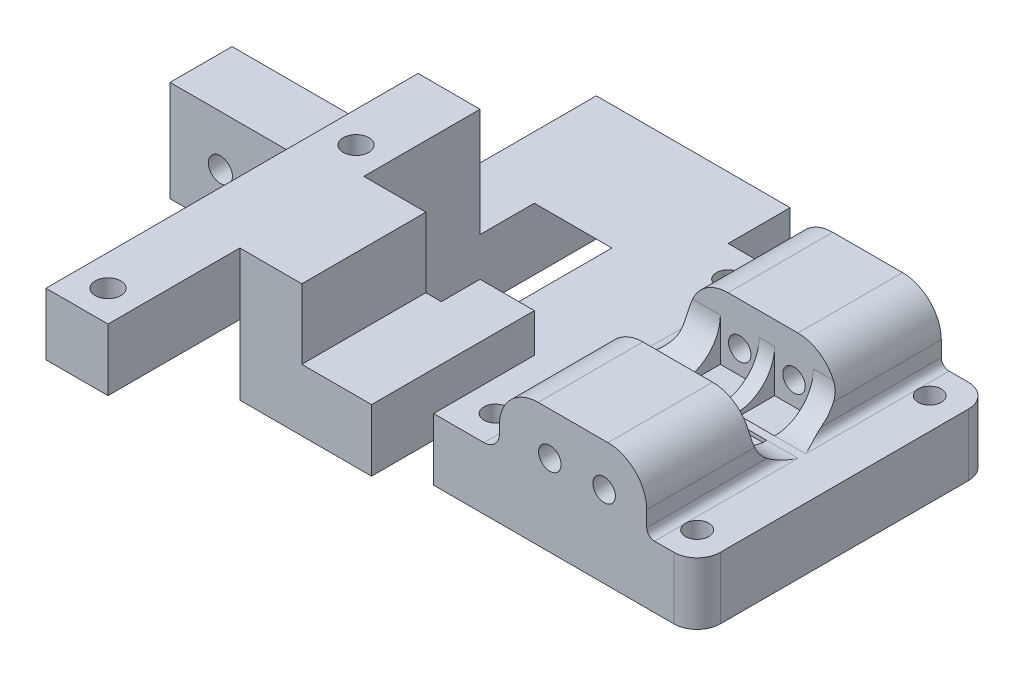
SolidWorks part; units mm, degrees
ref_plane "Front" through (0, 0, 0) normal (0, 0, 1) x (1, 0, 0)
ref_plane "Top" through (0, 0, 0) normal (0, 1, 0) x (1, 0, 0)
ref_plane "Right" through (0, 0, 0) normal (1, 0, 0) x (0, 0, -1)
sketch "Sketch1" plane through (0, 0, 0) normal (0, 1, 0) x (1, 0, 0)
  line L1 (0, 0) -> (300, 0)
  line L2 (0, 0) -> (0, -20)
  line L3 (0, -20) -> (300, -20)
  line L4 (300, 0) -> (300, -20)
  dimension "D1" = 20
  dimension "D2" = 300
extrude "Boss-Extrude1" add sketch "Sketch1" along normal blind 8
sketch "Sketch2" plane through (0, 0, 20) normal (0, 0, 1) x (1, 0, 0)
  line L0 (0, 8) -> (300, 8) construction
  line L1 (0, 0) -> (34, 0)
  line L2 (0, 0) -> (0, 8)
  line L3 (0, 8) -> (34, 8)
  line L4 (34, 0) -> (34, 8)
  line L5 (266, 8) -> (300, 8)
  line L6 (300, 0) -> (300, 8)
  line L7 (266, 0) -> (300, 0)
  line L8 (266, 0) -> (266, 8)
  dimension "D1" = 34
  dimension "D2" = 2
extrude "Boss-Extrude2" add sketch "Sketch2" along normal blind 9
sketch "Sketch3" plane through (0, 0, 0) normal (0, 0, -1) x (-1, 0, 0)
  line L0 (-300, 8) -> (0, 8) construction
  line L1 (0, 0) -> (-34, 0)
  line L2 (0, 0) -> (0, 8)
  line L3 (0, 8) -> (-34, 8)
  line L4 (-34, 0) -> (-34, 8)
  line L5 (-300, 0) -> (-300, 8)
  line L6 (-266, 8) -> (-300, 8)
  line L7 (-266, 0) -> (-266, 8)
  line L8 (-266, 0) -> (-300, 0)
  dimension "D1" = 34
  dimension "D2" = 2
extrude "Boss-Extrude3" add sketch "Sketch3" along normal blind 9
sketch "Sketch4" plane through (0, 8, 0) normal (0, 1, 0) x (1, 0, 0)
  line L0 (0, 9) -> (34, 9) construction
  line L1 (0, 9) -> (0, -29) construction
  circle A0 centre (4, 5) radius 1.5
  circle A1 centre (30, 5) radius 1.5
  circle A2 centre (30, -25) radius 1.5
  circle A3 centre (4, -25) radius 1.5
  circle A4 centre (296, -25) radius 1.5
  circle A5 centre (296, 5) radius 1.5
  circle A6 centre (270, -25) radius 1.5
  circle A7 centre (270, 5) radius 1.5
  dimension "D1" = 3
  dimension "D2" = 4
  dimension "D3" = 4
  dimension "D4" = 2
  dimension "D5" = 2
  dimension "D6" = 2
extrude "Cut-Extrude1" cut sketch "Sketch4" against normal through all
sketch "Sketch5" plane through (0, 0, 20) normal (0, 0, 1) x (1, 0, 0)
  line L0 (34, 8) -> (266, 8) construction
  line L1 (266, 0) -> (241, 0)
  line L2 (266, 0) -> (266, 8)
  line L3 (266, 8) -> (241, 8)
  line L4 (241, 0) -> (241, 8)
  dimension "D1" = 25
extrude "Boss-Extrude4" add sketch "Sketch5" along normal blind 17
sketch "Sketch6" plane through (0, 0, 0) normal (0, 0, -1) x (-1, 0, 0)
  line L0 (-266, 0) -> (-34, 0) construction
  line L1 (-266, 8) -> (-241, 8)
  line L2 (-266, 8) -> (-266, 0)
  line L3 (-266, 0) -> (-241, 0)
  line L4 (-241, 8) -> (-241, 0)
  dimension "D1" = 25
extrude "Boss-Extrude5" add sketch "Sketch6" along normal blind 17
sketch "Sketch12" plane through (0, 0, 37) normal (0, 0, 1) x (1, 0, 0)
  line L0 (241, 0) -> (266, 0) construction
  line L1 (241, 8) -> (249, 8)
  line L2 (241, 8) -> (241, 0)
  line L3 (241, 0) -> (249, 0)
  line L4 (249, 8) -> (249, 0)
  dimension "D1" = 8
extrude "Boss-Extrude7" add sketch "Sketch12" along normal blind 17
sketch "Sketch18" plane through (0, 0, -9) normal (0, 0, -1) x (-1, 0, 0)
  line L0 (0, 8) -> (-34, 8) construction
  line L1 (-25, 8) -> (-5, 8)
  line L2 (-25, 8) -> (-25, -5)
  line L3 (-25, -5) -> (-5, -5)
  line L4 (-5, 8) -> (-5, -5)
  line L6 (-34, 8) -> (-34, 0) construction
  dimension "D1" = 20
  dimension "D2" = 9
  dimension "D3" = 13
extrude "Boss-Extrude10" add sketch "Sketch18" along normal blind 12
sketch "Sketch19" plane through (5, 0, 0) normal (-1, 0, 0) x (0, 0, 1)
  line L0 (-21, -5) -> (-21, 8) construction
  line L2 (-21, -5) -> (-9, -5) construction
  circle A0 centre (-15, 0) radius 1.6
  dimension "D1" = 3.2
  dimension "D2" = 6
  dimension "D3" = 5
extrude "Cut-Extrude9" cut sketch "Sketch19" against normal blind 20
sketch "Sketch20" plane through (0, 0, 29) normal (0, 0, 1) x (1, 0, 0)
  line L0 (34, 8) -> (0, 8) construction
  line L1 (5, 8) -> (25, 8)
  line L2 (5, 8) -> (5, -5)
  line L3 (5, -5) -> (25, -5)
  line L4 (25, 8) -> (25, -5)
  line L6 (34, 0) -> (34, 8) construction
  dimension "D1" = 20
  dimension "D2" = 9
  dimension "D3" = 13
extrude "Boss-Extrude11" add sketch "Sketch20" along normal blind 12
sketch "Sketch21" plane through (5, 0, 0) normal (-1, 0, 0) x (0, 0, 1)
  line L0 (41, 8) -> (41, -5) construction
  line L1 (41, -5) -> (29, -5) construction
  circle A0 centre (35, 0) radius 1.6
  dimension "D1" = 3.2
  dimension "D2" = 6
  dimension "D3" = 5
extrude "Cut-Extrude10" cut sketch "Sketch21" against normal blind 20
sketch "Sketch22" plane through (0, 8, 0) normal (0, 1, 0) x (1, 0, 0)
  line L0 (241, 17) -> (241, 0) construction
  line L1 (259, 9) -> (249, 9)
  line L2 (259, 9) -> (259, -29)
  line L3 (259, -29) -> (249, -29)
  line L4 (249, 9) -> (249, -29)
  line L5 (241, 17) -> (266, 17) construction
  line L6 (266, -37) -> (249, -37) construction
  dimension "D1" = 8
  dimension "D2" = 10
  dimension "D3" = 8
  dimension "D4" = 8
extrude "Cut-Extrude11" cut sketch "Sketch22" against normal through all
sketch "Sketch23" plane through (0, 0, 0) normal (0, -1, 0) x (-1, 0, 0)
  line L0 (-259, -29) -> (-259, 9) construction
  line L1 (-259, -19) -> (-267, -19)
  line L2 (-259, -19) -> (-259, -1)
  line L3 (-259, -1) -> (-267, -1)
  line L4 (-267, -19) -> (-267, -1)
  line L5 (-249, -29) -> (-259, -29) construction
  dimension "D1" = 8
  dimension "D2" = 10
  dimension "D3" = 10
extrude "Cut-Extrude12" cut sketch "Sketch23" against normal blind 4
sketch "Sketch24" plane through (259, 0, 0) normal (-1, 0, 0) x (0, 0, 1)
  line L0 (-9, 0) -> (-9, 8)
  line L1 (-9, 8) -> (-1, 8)
  line L2 (29, 8) -> (-9, 8) construction
  line L3 (-1, 8) -> (-9, 0)
  line L4 (29, 0) -> (29, 8)
  line L5 (29, 8) -> (21, 8)
  line L6 (21, 8) -> (29, 0)
  dimension "D1" = 8
  dimension "D2" = 8
extrude "Boss-Extrude12" add sketch "Sketch24" along normal blind 10
sketch "Sketch25" plane through (267, 0, 0) normal (-1, 0, 0) x (0, 0, 1)
  line L0 (19, 0) -> (19, 4)
  line L1 (19, 4) -> (15, 4)
  line L2 (1, 4) -> (19, 4) construction
  line L3 (15, 4) -> (19, 0)
  line L4 (1, 4) -> (5, 4)
  line L5 (5, 4) -> (1, 0)
  line L6 (1, 0) -> (1, 4)
  dimension "D1" = 4
  dimension "D2" = 4
extrude "Boss-Extrude13" add sketch "Sketch25" along normal blind 8
sketch "Sketch26" plane through (0, 8, 0) normal (0, 1, 0) x (1, 0, 0)
  line L0 (249, 1) -> (249, -21) construction
  line L1 (241, -54) -> (249, -54)
  line L2 (241, -54) -> (241, -6)
  line L3 (241, -6) -> (249, -6)
  line L4 (249, -54) -> (249, -6)
  dimension "D1" = 48
extrude "Boss-Extrude14" add sketch "Sketch26" along normal blind 14
sketch "Sketch27" plane through (0, 8, 0) normal (0, 1, 0) x (1, 0, 0)
  line L0 (249, -21) -> (259, -21) construction
  line L1 (249, -37) -> (257, -37)
  line L2 (249, -37) -> (249, -21)
  line L3 (249, -21) -> (257, -21)
  line L4 (257, -37) -> (257, -21)
  dimension "D1" = 8
extrude "Boss-Extrude15" add sketch "Sketch27" along normal blind 14
sketch "Sketch28" plane through (0, 0, 0) normal (0, -1, 0) x (1, 0, 0)
  line L0 (249, -9) -> (249, 29) construction
  line L1 (241, 54) -> (249, 54)
  line L2 (241, 54) -> (241, 14)
  line L3 (241, 14) -> (249, 14)
  line L4 (249, 54) -> (249, 14)
  dimension "D1" = 40
extrude "Cut-Extrude13" cut sketch "Sketch28" against normal blind 14
sketch "Sketch30" plane through (257, 0, 0) normal (1, 0, 0) x (0, 0, -1)
  line L0 (-37, 22) -> (-21, 22) construction
  line L1 (-21, 22) -> (-37, 22)
  line L2 (-21, 22) -> (-21, 8)
  line L3 (-21, 8) -> (-37, 8)
  line L4 (-37, 22) -> (-37, 8)
extrude "Boss-Extrude16" add sketch "Sketch30" along normal blind 9
sketch "Sketch31" plane through (0, 0, 0) normal (0, -1, 0) x (-1, 0, 0)
  line L1 (-249, -37) -> (-266, -37)
  line L2 (-249, -37) -> (-249, -29)
  line L3 (-249, -29) -> (-266, -29)
  line L4 (-266, -37) -> (-266, -29)
extrude "Cut-Extrude14" cut sketch "Sketch31" against normal blind 5
sketch "Sketch32" plane through (266, 0, 0) normal (1, 0, 0) x (0, 0, -1)
  line L0 (-37, 5) -> (-37, 22) construction
  line L1 (-21, 22) -> (-37, 22)
  line L2 (-21, 22) -> (-21, 13)
  line L3 (-21, 13) -> (-37, 13)
  line L4 (-37, 22) -> (-37, 13)
  dimension "D1" = 9
extrude "Cut-Extrude15" cut sketch "Sketch32" against normal blind 9
sketch "Sketch33" plane through (249, 0, 0) normal (-1, 0, 0) x (0, 0, 1)
  line L0 (29, 5) -> (24, 5)
  line L1 (21, 8) -> (29, 0) construction
  line L2 (24, 5) -> (29, 0)
  line L3 (29, 0) -> (29, 5)
extrude "Cut-Extrude16" cut sketch "Sketch33" against normal blind 10
sketch "Sketch34" plane through (0, 0, 29) normal (0, 0, 1) x (1, 0, 0)
  line L1 (266, 5) -> (259, 5)
  line L2 (266, 5) -> (266, 0)
  line L3 (266, 0) -> (259, 0)
  line L4 (259, 5) -> (259, 0)
extrude "Cut-Extrude17" cut sketch "Sketch34" against normal blind 5
sketch "Sketch35" plane through (0, 0, 21) normal (0, 0, -1) x (-1, 0, 0)
  line L0 (-249, 8) -> (-259, 8) construction
  line L1 (-259, 8) -> (-266, 8)
  line L2 (-259, 8) -> (-259, 13)
  line L3 (-259, 13) -> (-266, 13)
  line L4 (-266, 8) -> (-266, 13)
  line L5 (-266, 8) -> (-259, 8) construction
  line L6 (-266, 8) -> (-266, 13) construction
extrude "Boss-Extrude17" add sketch "Sketch35" along normal blind 5
sketch "Sketch36" plane through (0, 22, 0) normal (0, 1, 0) x (1, 0, 0)
  line L0 (241, -54) -> (249, -54) construction
  line L1 (249, -54) -> (249, -37) construction
  circle A0 centre (245, -50) radius 1.65
  circle A1 centre (245, -18) radius 1.65
  dimension "D2" = 4
  dimension "D3" = 4
  dimension "D4" = 2
  dimension "D1" = 3.3
extrude "Cut-Extrude18" cut sketch "Sketch36" against normal through all
sketch "Sketch37" plane through (0, 8, 0) normal (0, 1, 0) x (1, 0, 0)
  line L0 (241, -6) -> (171, -6)
  line L1 (241, -6) -> (241, -14) construction
  line L2 (241, -6) -> (241, -14)
  line L3 (241, -14) -> (241, -20) construction
  line L4 (241, -14) -> (171, -14)
  line L5 (171, -14) -> (171, -6)
  dimension "D1" = 70
extrude "Boss-Extrude18" add sketch "Sketch37" along normal blind 5
sketch "Sketch39" plane through (0, 8, 0) normal (0, 1, 0) x (1, 0, 0)
  line L0 (34, -20) -> (241, -20) construction
  line L1 (241, -14) -> (175, -14)
  line L2 (241, -14) -> (241, -20)
  line L3 (241, -20) -> (175, -20)
  line L4 (175, -14) -> (175, -20)
  dimension "D1" = 66
extrude "Cut-Extrude19" cut sketch "Sketch39" against normal through all
sketch "Sketch40" plane through (0, 8, 0) normal (0, 1, 0) x (1, 0, 0)
  line L1 (5, 9) -> (25, 9)
  line L2 (5, 9) -> (5, 21)
  line L3 (5, 21) -> (25, 21)
  line L4 (25, 9) -> (25, 21)
extrude "Boss-Extrude19" add sketch "Sketch40" along normal blind 10
sketch "Sketch41" plane through (0, 18, 0) normal (0, 1, 0) x (1, 0, 0)
  line L0 (25, 21) -> (5, 21) construction
  line L1 (25, 21) -> (-3, 21)
  line L2 (25, 21) -> (25, 9)
  line L3 (25, 9) -> (-3, 9)
  line L4 (-3, 21) -> (-3, 9)
  line L5 (5, 9) -> (25, 9) construction
  line L6 (25, 9) -> (25, 21) construction
  line L7 (5, 21) -> (5, 9) construction
  dimension "D1" = 28
  dimension "D2" = 20
extrude "Boss-Extrude20" add sketch "Sketch41" along normal blind 5 and the other way blind 5
sketch "Sketch42" plane through (-3, 0, 0) normal (-1, 0, 0) x (0, 0, 1)
  line L0 (-21, 23) -> (-9, 23) construction
  line L1 (-9, 13) -> (-9, 23) construction
  circle A0 centre (-14, 18) radius 1.5
  dimension "D1" = 3
  dimension "D2" = 5
  dimension "D3" = 5
extrude "Cut-Extrude20" cut sketch "Sketch42" against normal blind 15
sketch "Sketch43" plane through (0, 8, 0) normal (0, 1, 0) x (1, 0, 0)
  line L1 (5, -41) -> (25, -41)
  line L2 (5, -41) -> (5, -29)
  line L3 (5, -29) -> (25, -29)
  line L4 (25, -41) -> (25, -29)
extrude "Boss-Extrude21" add sketch "Sketch43" along normal blind 10
sketch "Sketch44" plane through (0, 18, 0) normal (0, 1, 0) x (1, 0, 0)
  line L0 (25, -29) -> (5, -29) construction
  line L1 (-3, -29) -> (25, -29)
  line L2 (-3, -29) -> (-3, -41)
  line L3 (-3, -41) -> (25, -41)
  line L4 (25, -29) -> (25, -41)
  line L5 (5, -41) -> (25, -41) construction
  line L6 (25, -41) -> (25, -29) construction
  line L7 (5, -29) -> (5, -41) construction
  dimension "D1" = 28
  dimension "D2" = 20
extrude "Boss-Extrude22" add sketch "Sketch44" along normal blind 5 and the other way blind 5
sketch "Sketch45" plane through (-3, 0, 0) normal (-1, 0, 0) x (0, 0, 1)
  line L0 (29, 23) -> (41, 23) construction
  line L1 (41, 13) -> (41, 23) construction
  circle A0 centre (36, 18) radius 1.5
  dimension "D1" = 3
  dimension "D2" = 5
  dimension "D3" = 5
extrude "Cut-Extrude21" cut sketch "Sketch45" against normal blind 15
sketch "Sketch49" plane through (0, 8, 0) normal (0, 1, 0) x (1, 0, 0)
  line L0 (241, 0) -> (34, 0) construction
  line L1 (34, -20) -> (175, -20) construction
  line L2 (0, 9) -> (0, -29) construction
  circle A0 centre (78, -8) radius 1.45
  circle A1 centre (78, -12) radius 1.45
  dimension "D1" = 2.9
  dimension "D2" = 2.9
  dimension "D3" = 8
  dimension "D4" = 8
  dimension "D5" = 78
  dimension "D6" = 78
extrude "Cut-Extrude23" cut sketch "Sketch49" against normal through all
sketch "Sketch50" plane through (-3, 0, 0) normal (-1, 0, 0) x (0, 0, 1)
  line L1 (63.9113, -17.5223) -> (-35.1617, -17.5223)
  line L2 (63.9113, -17.5223) -> (63.9113, 34.5971)
  line L3 (63.9113, 34.5971) -> (-35.1617, 34.5971)
  line L4 (-35.1617, -17.5223) -> (-35.1617, 34.5971)
extrude "Cut-Extrude24" cut sketch "Sketch50" against normal blind 220
sketch "Sketch51" plane through (0, 8, 0) normal (0, 1, 0) x (1, 0, 0)
  line L0 (241, 0) -> (217, 0) construction
  line L1 (217, -6) -> (238, -6)
  line L2 (217, -6) -> (217, 0)
  line L3 (217, 0) -> (238, 0)
  line L4 (238, -6) -> (238, 0)
  dimension "D1" = 21
extrude "Cut-Extrude25" cut sketch "Sketch51" against normal through all
sketch "Sketch52" plane through (0, 0, 6) normal (0, 0, -1) x (-1, 0, 0)
  line L0 (-217, 13) -> (-217, 0) construction
  circle A0 centre (-223.5, 6.5) radius 1.55
  circle A1 centre (-231.5, 6.5) radius 1.55
  dimension "D1" = 3.1
  dimension "D2" = 3.1
  dimension "D3" = 6.5
  dimension "D4" = 8
extrude "Cut-Extrude26" cut sketch "Sketch52" against normal through all
fillet "Fillet5" radius 3 2 edges at (300, 4, -9) (300, 4, 29)
sketch "Sketch54" plane through (0, 8, 0) normal (0, 1, 0) x (1, 0, 0)
  line L0 (266, 9) -> (297, 9) construction
  line L1 (293.5, 9) -> (274.5, 9)
  line L2 (293.5, 9) -> (293.5, -4.5)
  line L3 (293.5, -4.5) -> (274.5, -4.5)
  line L4 (274.5, 9) -> (274.5, -4.5)
  line L5 (297, -29) -> (266, -29) construction
  line L6 (293.5, -29) -> (274.5, -29)
  line L7 (293.5, -29) -> (293.5, -15.5)
  line L8 (293.5, -15.5) -> (274.5, -15.5)
  line L9 (274.5, -29) -> (274.5, -15.5)
  line L10 (300, -26) -> (300, 6) construction
  dimension "D1" = 13.5
  dimension "D2" = 13.5
  dimension "D3" = 19
  dimension "D4" = 19
  dimension "D5" = 6.5
  dimension "D6" = 6.5
extrude "Boss-Extrude26" add sketch "Sketch54" along normal blind 8
fillet "Fillet6" radius 5 2 edges at (284, 8, 4.5) (284, 8, 15.5)
sketch "Sketch55" plane through (0, 0, -9) normal (0, 0, -1) x (-1, 0, 0)
  line L0 (-293.5, 16) -> (-274.5, 16) construction
  line L1 (-293.5, 16) -> (-293.5, 8) construction
  line L2 (-274.5, 16) -> (-274.5, 8) construction
  circle A0 centre (-288, 10.5) radius 1.45
  circle A1 centre (-281, 10.5) radius 1.45
  dimension "D1" = 2.9
  dimension "D2" = 2.9
  dimension "D3" = 5.5
  dimension "D4" = 5.5
  dimension "D5" = 5.5
  dimension "D6" = 6.5
extrude "Cut-Extrude27" cut sketch "Sketch55" against normal through all
fillet "Fillet7" radius 5 4 edges at (274.5, 16, -2.25) (293.5, 16, -2.25) (274.5, 16, 22.25) (293.5, 16, 22.25)
fillet "Fillet8" radius 1 2 edges at (293.5, 8, 0.25) (293.5, 8, 19.75)
fillet "Fillet9" radius 2 2 edges at (274.5, 8, 0.25) (274.5, 8, 19.75)
sketch "Sketch56" plane through (0, 16, 0) normal (0, 1, 0) x (1, 0, 0)
  line L0 (288.5, -15.5) -> (279.5, -15.5) construction
  line L1 (288.5, -29) -> (288.5, -15.5) construction
  line L2 (283.5, -15.5) -> (278.5, -15.5)
  line L3 (283.5, -15.5) -> (283.5, -10.5)
  line L4 (283.5, -10.5) -> (278.5, -10.5)
  line L5 (285.5, -15.5) -> (290.5, -15.5)
  line L6 (285.5, -15.5) -> (285.5, -10.5)
  line L7 (285.5, -10.5) -> (290.5, -10.5)
  line L8 (290.5, -15.5) -> (290.5, -10.5)
  line L9 (279.5, -4.5) -> (288.5, -4.5) construction
  line L10 (283.5, -4.5) -> (278.5, -4.5)
  line L11 (283.5, -4.5) -> (283.5, -9.5)
  line L12 (283.5, -9.5) -> (278.5, -9.5)
  line L13 (278.5, -4.5) -> (278.5, -9.5)
  line L14 (278.5, -15.5) -> (278.5, -10.5)
  line L15 (285.5, -4.5) -> (290.5, -4.5)
  line L16 (285.5, -4.5) -> (285.5, -9.5)
  line L17 (285.5, -9.5) -> (290.5, -9.5)
  line L18 (290.5, -4.5) -> (290.5, -9.5)
  line L19 (279.5, -15.5) -> (279.5, -29) construction
  line L20 (288.5, -4.5) -> (288.5, 9) construction
  line L21 (279.5, 9) -> (279.5, -4.5) construction
  dimension "D1" = 5
  dimension "D2" = 5
  dimension "D3" = 5
  dimension "D4" = 5
  dimension "D5" = 5
  dimension "D6" = 5
  dimension "D7" = 5
  dimension "D8" = 5
  dimension "D9" = 3
  dimension "D10" = 4
  dimension "D11" = 3
  dimension "D12" = 4
extrude "Cut-Extrude28" cut sketch "Sketch56" against normal blind 8.5
equation "\"滑动-垂直孔\" = 0.6"
equation "\"滑动-水平孔\"= 0.3"
equation "\"松动-垂直孔\" = 0.3"
equation "\"松动-水平孔\"= 0.1"
equation "\"正常-垂直孔\" = 0.15"
equation "\"正常-水平孔\"= 0"
equation "\"紧缩-垂直孔\"= 0"
equation "\"紧缩-水平孔\"= - 0.1"
equation "\"D1@Sketch4\"=\"紧缩-垂直孔\"+3"
equation "\"D2@Sketch55\"=\"紧缩-水平孔\"+3"
equation "\"D1@Sketch55\"=\"紧缩-水平孔\"+3"
equation "\"D1@Sketch36\"=\"松动-垂直孔\"+3"
equation "\"D1@Sketch52\"=\"松动-水平孔\"+3"
equation "\"D2@Sketch52\"=\"松动-水平孔\"+3"
